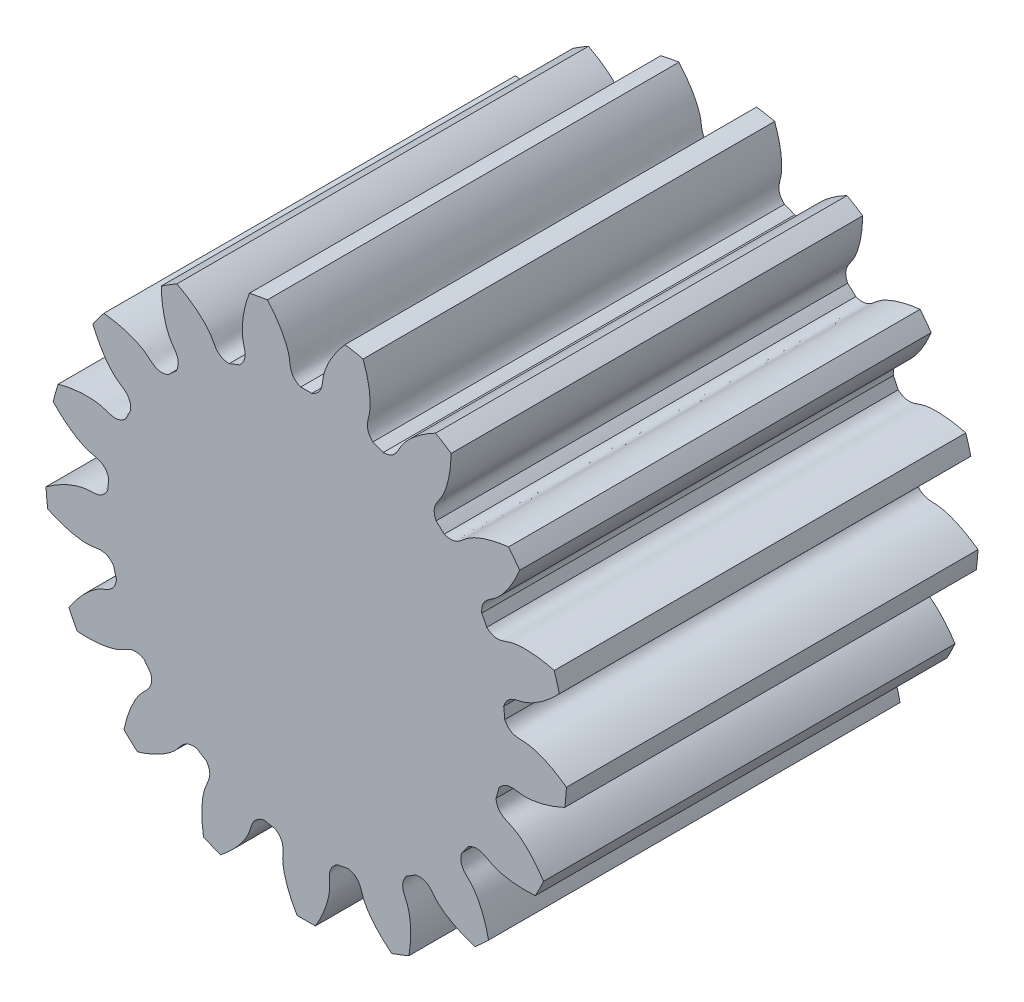
SolidWorks part; units mm, degrees
ref_plane "前视基准面" through (0, 0, 0) normal (0, 0, 1) x (1, 0, 0)
ref_plane "上视基准面" through (0, 0, 0) normal (0, 1, 0) x (1, 0, 0)
ref_plane "右视基准面" through (0, 0, 0) normal (1, 0, 0) x (0, 0, -1)
sketch "草图1" plane through (0, 0, 0) normal (0, 0, 1) x (1, 0, 0)
  circle A0 centre (0, 0) radius 19
extrude "凸台-拉伸1" add sketch "草图1" along normal blind 30
ref_axis "基准轴1" through (0, 0, -1.5) along (0, 0, 1)
sketch "草图2" plane through (0, 0, 0) normal (0, 0, 1) x (1, 0, 0)
  line L0 (0, 0) -> (0, 19) construction
  circle A0 centre (0, 0) radius 19 construction
  arc A1 (0.4034, 14.4944) -> (-0.4034, 14.4944) centre (0, 0) ccw
  arc A2 (6.2313, 21.4814) -> (-6.2313, 21.4814) centre (0, 0) ccw
  spline S0 degree 3 poles (0.4034, 14.4944) (1.2558, 14.8496) (1.1324, 15.5096) (1.2766, 16.1296) (1.29, 16.1823) (1.306, 16.2408) (1.3251, 16.3052) (1.3474, 16.3752) (1.3731, 16.4508) (1.4025, 16.5319) (1.4359, 16.6184) (1.4733, 16.7101) (1.5152, 16.8068) (1.5616, 16.9086) (1.6128, 17.0151) (1.669, 17.1264) (1.7304, 17.2421) (1.7972, 17.3621) (1.8696, 17.4863) (1.9478, 17.6145) (2.032, 17.7465) (2.1224, 17.8821) (2.2191, 18.0211) (2.3223, 18.1634) (2.4322, 18.3086) (2.5489, 18.4566) (2.6727, 18.6072) (2.8035, 18.7601) (2.9417, 18.9152) (3.0873, 19.0722) (3.2404, 19.2308) (3.4012, 19.3908) (3.5698, 19.552) (3.7462, 19.7141) (3.9307, 19.8769) (4.1233, 20.0401) (4.324, 20.2035) (4.533, 20.3667) (4.7503, 20.5295) (4.9761, 20.6917) (5.2103, 20.853) (5.453, 21.0131) (5.7916, 21.2269) (6.0532, 21.3811) (6.2313, 21.4814) knots 0 0 0 0 0.193883 0.199024 0.204851 0.211363 0.21856 0.226443 0.235011 0.244265 0.254205 0.264829 0.27614 0.288136 0.300817 0.314184 0.328236 0.342973 0.358397 0.374505 0.391299 0.408779 0.426944 0.445795 0.465331 0.485552 0.506459 0.528051 0.550329 0.573293 0.596941 0.621276 0.646296 0.672001 0.698392 0.725468 0.753229 0.781677 0.810809 0.840627 0.871131 0.90232 0.934195 1 1 1 1
  spline S1 degree 3 poles (-0.4034, 14.4944) (-1.2558, 14.8496) (-1.1324, 15.5096) (-1.2766, 16.1296) (-1.29, 16.1823) (-1.306, 16.2408) (-1.3251, 16.3052) (-1.3474, 16.3752) (-1.3731, 16.4508) (-1.4025, 16.5319) (-1.4359, 16.6184) (-1.4733, 16.7101) (-1.5152, 16.8068) (-1.5616, 16.9086) (-1.6128, 17.0151) (-1.669, 17.1264) (-1.7304, 17.2421) (-1.7972, 17.3621) (-1.8696, 17.4863) (-1.9478, 17.6145) (-2.032, 17.7465) (-2.1224, 17.8821) (-2.2191, 18.0211) (-2.3223, 18.1634) (-2.4322, 18.3086) (-2.5489, 18.4566) (-2.6727, 18.6072) (-2.8035, 18.7601) (-2.9417, 18.9152) (-3.0873, 19.0722) (-3.2404, 19.2308) (-3.4012, 19.3908) (-3.5698, 19.552) (-3.7462, 19.7141) (-3.9307, 19.8769) (-4.1233, 20.0401) (-4.324, 20.2035) (-4.533, 20.3667) (-4.7503, 20.5295) (-4.9761, 20.6917) (-5.2103, 20.853) (-5.453, 21.0131) (-5.7916, 21.2269) (-6.0532, 21.3811) (-6.2313, 21.4814) knots 0 0 0 0 0.193883 0.199024 0.204851 0.211363 0.21856 0.226443 0.235011 0.244265 0.254205 0.264829 0.27614 0.288136 0.300817 0.314184 0.328236 0.342973 0.358397 0.374505 0.391299 0.408779 0.426944 0.445795 0.465331 0.485552 0.506459 0.528051 0.550329 0.573293 0.596941 0.621276 0.646296 0.672001 0.698392 0.725468 0.753229 0.781677 0.810809 0.840627 0.871131 0.90232 0.934195 1 1 1 1
extrude "切除-拉伸1" cut sketch "草图2" along normal through all
pattern_circular "阵列(圆周)1" count 17 every 21.176 about axis through (0, 0, -1.5) along (0, 0, 1) of "切除-拉伸1"
sketch "草图3" plane through (0, 0, 0) normal (0, 0, 1) x (1, 0, 0)
  circle A0 centre (0, 0) radius 17 construction
  dimension "Dn" = 34
